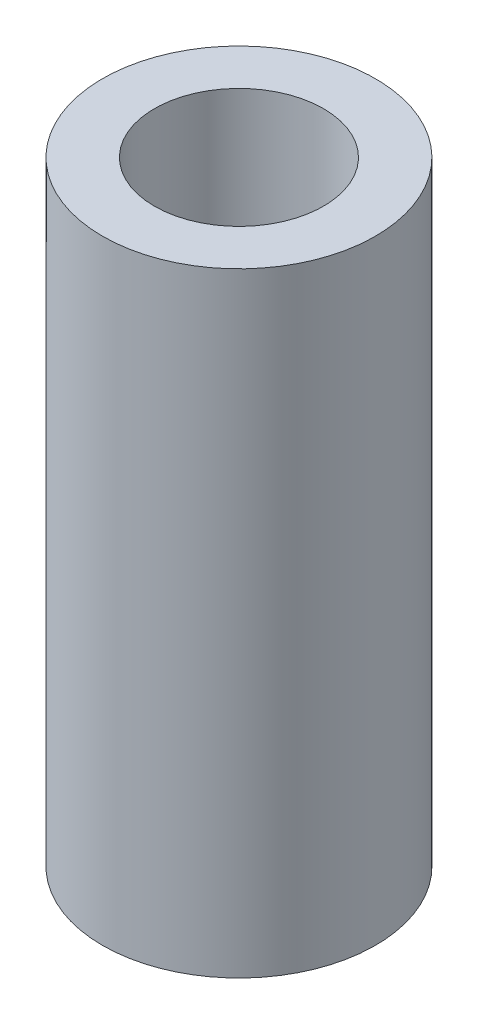
SolidWorks part; units mm, degrees
ref_plane "Front Plane" through (0, 0, 0) normal (0, 0, 1) x (1, 0, 0)
ref_plane "Top Plane" through (0, 0, 0) normal (0, 1, 0) x (1, 0, 0)
ref_plane "Right Plane" through (0, 0, 0) normal (1, 0, 0) x (0, 0, -1)
sketch "Sketch1" plane through (0, 0, 0) normal (0, 1, 0) x (1, 0, 0)
  circle A0 centre (0, 0) radius 12.5
  dimension "SLEEVE_OD" = 25
extrude "Boss-Extrude1" add sketch "Sketch1" along normal blind 56.2608
sketch "Sketch2" plane through (0, 0, 0) normal (0, 1, 0) x (1, 0, 0)
  circle A0 centre (0, 0) radius 7.7441
  dimension "BORE_D" = 15.4882
extrude "Cut-Extrude1" cut sketch "Sketch2" along normal through all
chamfer "Chamfer1" distance 1.7629 angle 60 rebuild error yes
